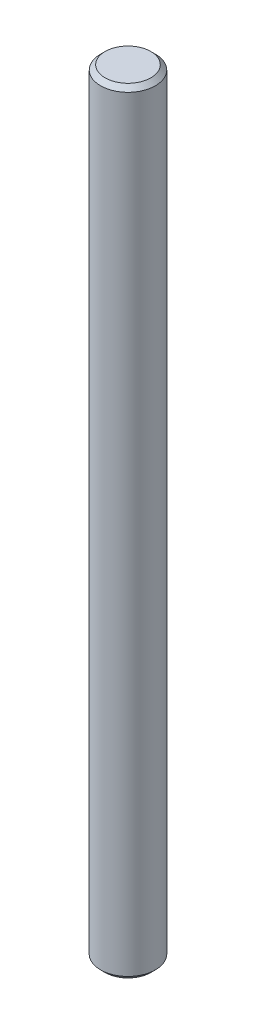
SolidWorks part; units mm, degrees
ref_plane "Front Plane" through (0, 0, 0) normal (0, 0, 1) x (1, 0, 0)
ref_plane "Top Plane" through (0, 0, 0) normal (0, 1, 0) x (1, 0, 0)
ref_plane "Right Plane" through (0, 0, 0) normal (1, 0, 0) x (0, 0, -1)
sketch "Sketch1" plane through (0, 0, 0) normal (0, 1, 0) x (1, 0, 0)
  circle A0 centre (0, 0) radius 3
  dimension "D1" = 6
extrude "Boss-Extrude1" add sketch "Sketch1" along normal blind 84.75
chamfer "Chamfer1" distance 0.5 angle 45 2 edges at (0, 0, 3) (0, 84.75, 3)
